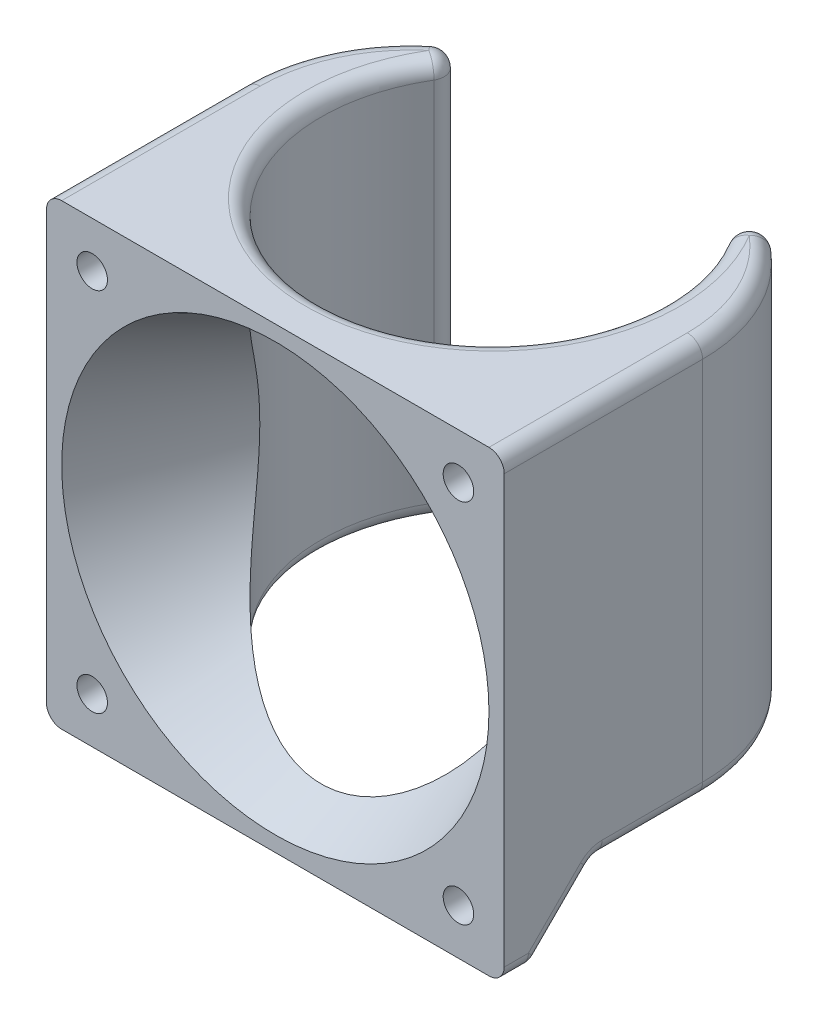
SolidWorks part; units mm, degrees
ref_plane "Front" through (0, 0, 0) normal (0, 0, 1) x (1, 0, 0)
ref_plane "Top" through (0, 0, 0) normal (0, 1, 0) x (1, 0, 0)
ref_plane "Right" through (0, 0, 0) normal (1, 0, 0) x (0, 0, -1)
sketch "Esboço1" plane through (0, 0, 0) normal (0, 1, 0) x (1, 0, 0)
  line L0 (-15, 0) -> (15, 0)
  line L1 (-15, 0) -> (-15, 13)
  line L3 (15, 13) -> (15, 0)
  line L4 (0, 3) -> (0, 0) construction
  line L5 (0, 3) -> (0, 14.25) construction
  line L6 (-15, 13) -> (15, 13) construction
  line L7 (-10.5, 20.5597) -> (10.5, 20.5597) construction
  arc A0 (-9.6429, 20.0446) -> (9.6429, 20.0446) centre (0, 14.25) ccw
  arc A1 (-9.6429, 20.0446) -> (-11.147, 21.3222) centre (-10.5, 20.5597) ccw
  arc A2 (9.6429, 20.0446) -> (11.147, 21.3222) centre (10.5, 20.5597) cw
  arc A3 (-11.147, 21.3222) -> (-15, 13) centre (-4.0858, 13) ccw
  arc A4 (11.147, 21.3222) -> (15, 13) centre (4.0858, 13) cw
  dimension "D2" = 11.25
  dimension "D4" = 1
  dimension "D1" = 30
  dimension "D3" = 3
  dimension "D5" = 21
  dimension "D6" = 13
extrude "Ressalto-extrusão1" add sketch "Esboço1" along normal mid plane 30
sketch "Esboço2" plane through (0, 0, 0) normal (0, 0, 1) x (1, 0, 0)
  line L1 (12, -12) -> (-12, -12) construction
  line L2 (12, -12) -> (12, 12) construction
  line L3 (12, 12) -> (-12, 12) construction
  line L4 (-12, -12) -> (-12, 12) construction
  line L5 (12, -12) -> (-12, 12) construction
  line L6 (12, 12) -> (-12, -12) construction
  circle A0 centre (-12, 12) radius 1
  circle A1 centre (12, 12) radius 1
  circle A2 centre (12, -12) radius 1
  circle A3 centre (-12, -12) radius 1
  point P0 (0, 0)
  dimension "D2" = 2
  dimension "D1" = 24
extrude "Corte-extrusão1" cut sketch "Esboço2" against normal blind 6
sketch "Esboço3" plane through (0, 0, 0) normal (0, 0, 1) x (1, 0, 0)
  circle A0 centre (0, 0) radius 14
  dimension "D1" = 28
extrude "Corte-extrusão2" cut sketch "Esboço3" against normal blind 10 draft 25
sketch "Esboço5" plane through (0, 0, 0) normal (1, 0, 0) x (0, 0, -1)
  line L0 (2, -15) -> (6, -11)
  line L1 (0, -15) -> (13, -15) construction
  line L2 (6, -11) -> (21.5597, -11)
  line L3 (21.5597, -15) -> (21.5597, 15) construction
  line L4 (21.5597, -11) -> (21.5597, -15)
  line L5 (21.5597, -15) -> (2, -15)
  line L6 (0, 15) -> (0, -15) construction
  dimension "D1" = 4
  dimension "D2" = 2
  dimension "D3" = 45
extrude "Corte-extrusão3" cut sketch "Esboço5" against normal through all both and the other way through all
fillet "Filete1" radius 1 5 edges at (-13.5, -11, -6) (9.8243, -11, -6) (-9.8243, -11, -6) (13.5, -11, -6) (0, -15, -2)
fillet "Filete2" radius 1 26 edges at (-15, 15, -6.5) (-13.99, 15, -17.5854) (-9.8526, 15, -21.3219) (0, 15, -3) (9.8526, 15, -21.3219) (13.99, 15, -17.5854) (-15, -15, -0.7929) (-15, -14.9239, -1.9685) (-15, -13, -4) (-15, -11.0761, -6.0315) (-15, -11, -9.7071) (-13.99, -11, -17.5854) (-9.8526, -11, -21.3219) (-11.1761, -11, -12.9623) (-7.6634, -11.0837, -6.0138) (0, -14, -3) (7.6025, -11.1103, -5.9576) (11.1761, -11, -12.9623) (9.8526, -11, -21.3219) (13.99, -11, -17.5854) (15, -11, -9.7071) (15, -11.0761, -6.0315) (15, -13, -4) (15, -14.9239, -1.9685) (15, 15, -6.5) (15, -15, -0.7929)
